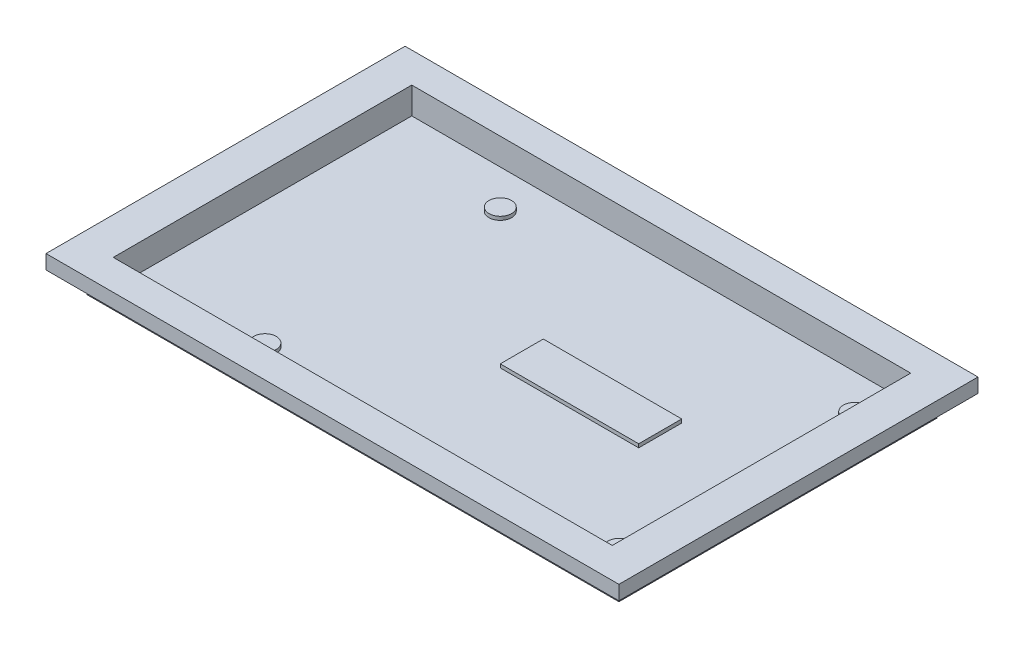
SolidWorks part; units mm, degrees
material "ABS"
ref_plane "Front Plane" through (0, 0, 0) normal (0, 0, 1) x (1, 0, 0)
ref_plane "Top Plane" through (0, 0, 0) normal (0, 1, 0) x (1, 0, 0)
ref_plane "Right Plane" through (0, 0, 0) normal (1, 0, 0) x (0, 0, -1)
sketch "Sketch1" plane through (0, 0, 0) normal (0, 1, 0) x (1, 0, 0)
  line L1 (0, 0) -> (64.3, 0)
  line L2 (0, 0) -> (0, 40.3)
  line L3 (0, 40.3) -> (64.3, 40.3)
  line L4 (64.3, 0) -> (64.3, 40.3)
  dimension "D1" = 64.3
  dimension "D2" = 40.3
extrude "Boss-Extrude1" add sketch "Sketch1" along normal blind 4
sketch "Sketch2" plane through (0, 4, 0) normal (0, 1, 0) x (1, 0, 0)
  line L1 (0, 0) -> (64.3, 40.3) construction
  line L2 (32.15, 0) -> (32.15, 40.3)
  line L3 (64.3, 40.3) -> (0, 40.3) construction
  line L4 (0, 20.15) -> (64.3, 20.15)
  line L6 (64.3, 0) -> (64.3, 40.3) construction
  line L10 (4.15, 36.9) -> (60.15, 36.9)
  line L11 (4.15, 36.9) -> (4.15, 3.4)
  line L12 (4.15, 3.4) -> (60.15, 3.4)
  line L13 (60.15, 36.9) -> (60.15, 3.4)
  point P7 (32.15, 20.15)
  point P14 (32.15, 20.15)
  dimension "D1" = 56
  dimension "D2" = 33.5
  dimension "D3" = 28
  dimension "D4" = 16.75
extrude "main well cutout" cut sketch "Sketch2" against normal blind 3 contours L10 L11 L4 L2 | L2 L1 L10 | L1 L4 L13 L10 | L13 L4 L2 L12 | L1 L12 L2 | L12 L1 L4 L11 region at (13.5018, 4, -14.3235) region at (23.2416, 4, -8.9833) region at (41.0584, 4, -31.3167) region at (46.15, 4, -11.775) region at (18.15, 4, -28.525) region at (50.7982, 4, -25.9765)
sketch "Sketch5" plane through (0, 0, 0) normal (0, 0, 1) x (1, 0, 0)
  line L0 (64.3, 4) -> (64.3, 0) construction
  line L1 (0, 0) -> (64.3, 0)
  line L2 (0, 0) -> (0, 2.4)
  line L3 (0, 2.4) -> (64.3, 2.4)
  line L4 (64.3, 0) -> (64.3, 2.4)
  line L6 (0, 0) -> (2.3, 0)
  line L7 (0, 0) -> (0, 2.4)
  line L8 (0, 2.4) -> (2.3, 2.4)
  line L9 (2.3, 0) -> (2.3, 2.4)
  line L10 (64.3, 0) -> (62, 0)
  line L11 (64.3, 0) -> (64.3, 2.4)
  line L12 (64.3, 2.4) -> (62, 2.4)
  line L13 (62, 0) -> (62, 2.4)
  line M2 (0, 0) -> (64.3, 0)
  line M3 (64.3, 0) -> (64.3, 4)
  line M5 (0, 4) -> (0, 0)
  dimension "D1" = 2.4
  dimension "D2" = 2.3
  dimension "D3" = 2.3
sketch "Sketch8" plane through (0, 1, 0) normal (0, 1, 0) x (1, 0, 0)
  line L0 (4.15, 3.4) -> (60.15, 3.4) construction
  line L1 (33.614, 22.196) -> (49.15, 22.196)
  line L2 (33.614, 22.196) -> (33.614, 17.37)
  line L3 (33.614, 17.37) -> (49.15, 17.37)
  line L4 (49.15, 22.196) -> (49.15, 17.37)
  line L5 (4.15, 3.4) -> (60.15, 3.4) construction
  line L6 (4.15, 36.9) -> (4.15, 3.4) construction
  line L7 (4.15, 36.9) -> (4.15, 3.4) construction
  circle A0 centre (18.374, 32.61) radius 1.27
  circle A1 centre (18.374, 6.194) radius 1.27
  circle A2 centre (58.15, 6.194) radius 1.27
  circle A3 centre (58.15, 32.61) radius 1.27
  dimension "D1" = 2.54
  dimension "D2" = 2.54
  dimension "D3" = 2.54
  dimension "D4" = 2.54
  dimension "D5" = 2.794
  dimension "D6" = 2.794
  dimension "D7" = 29.21
  dimension "D8" = 29.21
  dimension "D9" = 14.224
  dimension "D10" = 14.224
  dimension "D11" = 54
  dimension "D12" = 54
  dimension "D13" = 13.97
  dimension "D14" = 18.796
  dimension "D15" = 29.464
  dimension "D16" = 45
extrude "Adhesive contact" add sketch "Sketch8" along normal blind 0.4
extrude "Cut-Extrude2" cut sketch "Sketch5" against normal blind 2.3 contours L1 L13 L3 L9 region at (32.15, 1.2, 0)
extrude "Cut-Extrude3" cut sketch "Sketch5<3>" against normal through all contours L9 L3 M2 M5 | L13 L3 M2 M3 region at (1.15, 1.2, 0) region at (63.15, 1.2, 0)
sketch "Sketch5<3>" plane through (0, 0, 0) normal (0, 0, 1) x (1, 0, 0) same geometry as "Sketch5"
sketch "midpt" plane through (0, 4, 0) normal (0, 1, 0) x (1, 0, 0)
  line L0 (0, 0) -> (64.3, 40.3) construction
  line L1 (64.3, 20.15) -> (0, 20.15)
  line L2 (0, 40.3) -> (0, 0) construction
  point P9 (32.15, 20.15)
ref_plane "midpt plane" through (0, 0, -20.15) normal (0, 0, 1) x (1, 0, 0)
mirror "cuttout mirror" about plane through (0, 0, -20.15) normal (0, 0, 1) of "Cut-Extrude2"
